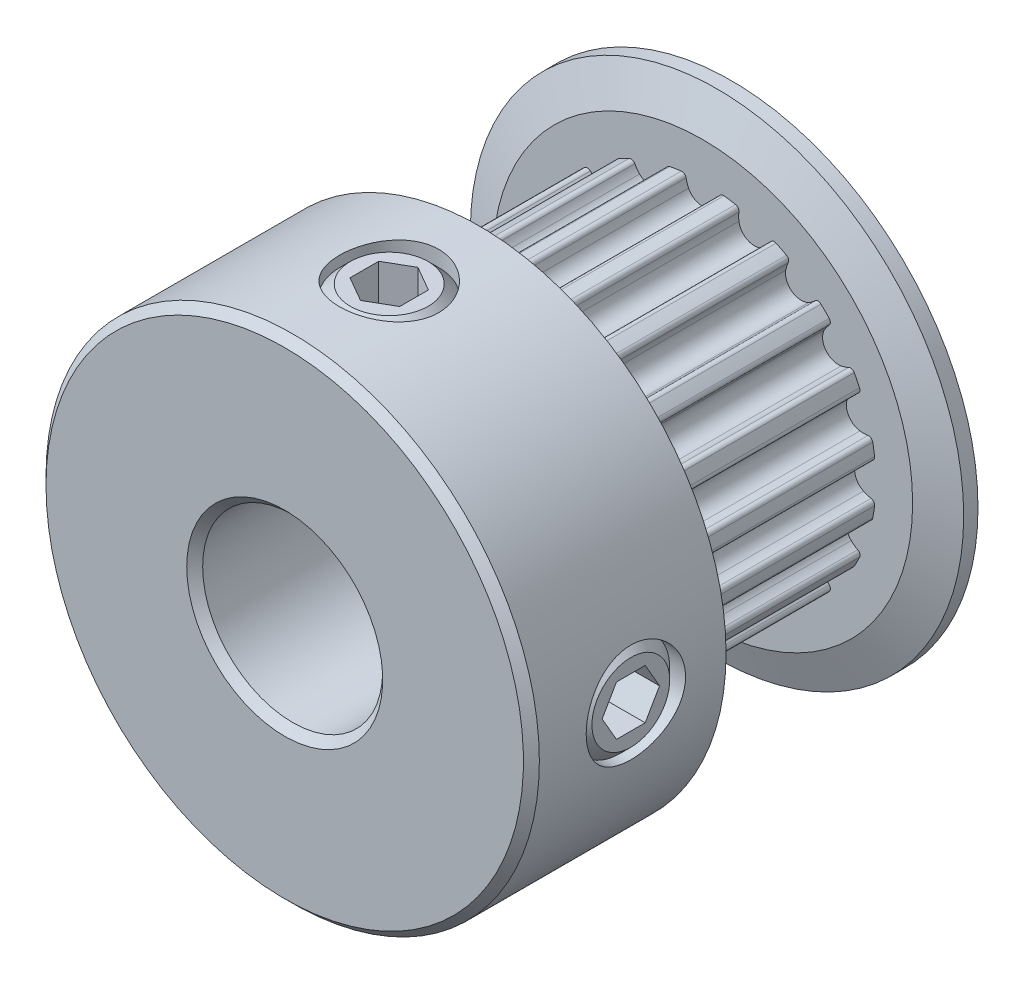
SolidWorks part; units mm, degrees
ref_plane "Front Plane" through (0, 0, 0) normal (0, 0, 1) x (1, 0, 0)
ref_plane "Top Plane" through (0, 0, 0) normal (0, 1, 0) x (1, 0, 0)
ref_plane "Right Plane" through (0, 0, 0) normal (1, 0, 0) x (0, 0, -1)
sketch "Sketch1" plane through (0, 0, 0) normal (0, 0, 1) x (1, 0, 0)
  line L1 (-1.7499, 5.3585) -> (1.7499, 5.3585) construction
  line L4 (0, 0) -> (0, 5.3585) construction
  line L5 (0, 5.3585) -> (0, 11.211) construction
  line L6 (0, 6.3625) -> (1.9751, 6.0482) construction
  line L7 (1.9751, 6.0482) -> (2.6648, 5.8229) construction
  line L8 (1.9751, 6.0482) -> (1.7499, 5.3585) construction
  line L9 (-1.9751, 6.0482) -> (-1.7499, 5.3585) construction
  line L10 (-1.8963, 5.8067) -> (-2.841, 8.6995)
  line L11 (-2.841, 8.6995) -> (2.841, 8.6995)
  line L12 (2.841, 8.6995) -> (1.8963, 5.8067)
  circle A0 centre (0, 0) radius 6.3625 construction
  circle A1 centre (0, 0) radius 8.6995 construction
  circle A2 centre (0, 0) radius 6.1085 construction
  arc A3 (-0.4989, 5.6703) -> (0.4989, 5.6703) centre (0, 5.9135) ccw
  arc A4 (-0.4989, 5.6703) -> (-0.5855, 5.9387) centre (0.4, 6.1085) cw
  arc A5 (-1.8963, 5.8067) -> (-0.7518, 6.0621) centre (0, 0) cw
  arc A6 (-0.5855, 5.9387) -> (-0.7518, 6.0621) centre (-0.7333, 5.9132) ccw
  arc A7 (1.8963, 5.8067) -> (0.7518, 6.0621) centre (0, 0) ccw
  arc A8 (0.5855, 5.9387) -> (0.7518, 6.0621) centre (0.7333, 5.9132) cw
  arc A9 (0.4989, 5.6703) -> (0.5855, 5.9387) centre (-0.4, 6.1085) ccw
  point P6 (0, 20.9083)
  point P11 (0, 6.3625)
  point P13 (0, 8.6995)
  point P14 (0, 6.1085)
  dimension "D1" = 9.6973
  dimension "D2" = 4.8485
sketch "Sketch2" plane through (0, 0, 0) normal (1, 0, 0) x (0, 0, -1)
  line L0 (-7.875, 3.175) -> (7.875, 3.175)
  line L1 (-7.875, 3.175) -> (-7.875, 8.6995)
  line L2 (-1.01, 8.6995) -> (-7.875, 8.6995)
  line L3 (-1.515, 3.175) -> (-1.515, 8.6995) construction
  line L4 (-1.515, 8.6995) -> (-0.505, 8.6995) construction
  line L5 (-0.505, 8.6995) -> (-0.505, 6.1085) construction
  line L6 (-0.505, 6.1085) -> (6.865, 6.1085)
  line L7 (6.865, 6.1085) -> (6.865, 8.6995) construction
  line L8 (6.865, 8.6995) -> (7.875, 8.6995) construction
  line L9 (7.875, 8.6995) -> (7.875, 3.175)
  line L10 (-7.875, 0) -> (7.875, 0) construction
  line L11 (7.37, 8.6995) -> (6.865, 7.404)
  line L12 (-0.505, 7.404) -> (-1.01, 8.6995)
  line L14 (-0.505, 7.404) -> (-0.505, 6.1085)
  line L15 (6.865, 6.1085) -> (6.865, 7.404)
  line L16 (7.37, 8.6995) -> (7.875, 8.6995)
  arc A0 (-0.505, 7.404) -> (-1.01, 8.6995) centre (-2.4192, 7.404) ccw construction
  arc A1 (6.865, 7.404) -> (7.37, 8.6995) centre (8.7792, 7.404) cw construction
  point P12 (-0.505, 7.404)
  point P14 (-1.01, 8.6995)
  point P20 (6.865, 7.404)
  point P21 (7.37, 8.6995)
  point P25 (6.865, 0)
  point P26 (-0.505, 0)
  dimension "OA" = 15.75
  dimension "Bore" = 6.35
  dimension "Outside Width" = 8.38
  dimension "Inside Width" = 7.37
revolve "Revolve1" add sketch "Sketch2" angle 360 mid plane about L10
sketch "Sketch3" plane through (0, 0, 0) normal (0, 0, 1) x (1, 0, 0)
  line L6 (2.841, 8.6995) -> (-2.841, 8.6995)
  line L7 (1.8963, 5.8067) -> (2.841, 8.6995)
  line L8 (-2.841, 8.6995) -> (-1.8963, 5.8067)
  line L9 (2.841, 8.6995) -> (-2.841, 8.6995)
  line L10 (1.8963, 5.8067) -> (2.841, 8.6995)
  line L11 (-2.841, 8.6995) -> (-1.8963, 5.8067)
  arc A8 (1.8963, 5.8067) -> (0.7518, 6.0621) centre (0, 0) ccw
  arc A9 (0.7518, 6.0621) -> (0.5855, 5.9387) centre (0.7333, 5.9132) ccw
  arc A10 (0.4989, 5.6703) -> (0.5855, 5.9387) centre (-0.4, 6.1085) ccw
  arc A11 (-0.4989, 5.6703) -> (0.4989, 5.6703) centre (0, 5.9135) ccw
  arc A12 (-0.5855, 5.9387) -> (-0.4989, 5.6703) centre (0.4, 6.1085) ccw
  arc A13 (-0.5855, 5.9387) -> (-0.7518, 6.0621) centre (-0.7333, 5.9132) ccw
  arc A14 (-0.7518, 6.0621) -> (-1.8963, 5.8067) centre (0, 0) ccw
  arc A15 (1.8963, 5.8067) -> (0.7518, 6.0621) centre (0, 0) ccw
  arc A16 (0.7518, 6.0621) -> (0.5855, 5.9387) centre (0.7333, 5.9132) ccw
  arc A17 (0.4989, 5.6703) -> (0.5855, 5.9387) centre (-0.4, 6.1085) ccw
  arc A18 (-0.4989, 5.6703) -> (0.4989, 5.6703) centre (0, 5.9135) ccw
  arc A19 (-0.5855, 5.9387) -> (-0.4989, 5.6703) centre (0.4, 6.1085) ccw
  arc A20 (-0.5855, 5.9387) -> (-0.7518, 6.0621) centre (-0.7333, 5.9132) ccw
  arc A21 (-0.7518, 6.0621) -> (-1.8963, 5.8067) centre (0, 0) ccw
  dimension "D1" = 0
extrude "Cut-Extrude1" cut sketch "Sketch3" against normal up to vertex (6.865 mm away) from vertex up to point (0, 6.1085, -6.865) starting at point (0, 6.1085, 0.505)
pattern_circular "CirPattern1" count 20 over 360 about axis through (0, 0, 7.875) along (0, 0, 1) of "Cut-Extrude1"
sketch "Sketch4" plane through (0, 0, 0) normal (1, 0, 0) x (0, -1, 0)
  line L0 (0, -0.505) -> (0, -7.875) construction
  line L1 (-3.175, -7.875) -> (3.175, -7.875) construction
  line L2 (7.404, -0.505) -> (-7.404, -0.505) construction
  circle A0 centre (0, -4.19) radius 1.7526
extrude "Cut-Extrude2" cut sketch "Sketch4" along normal through all
ref_plane "Plane1" through (0, 0, 4.19) normal (0, 0, 1) x (1, 0, 0)
sketch "Sketch5" plane through (0, 0, 4.19) normal (0, 0, 1) x (1, 0, 0)
  line L0 (0, 0) -> (0, 8.6995) construction
  line L1 (3.175, -1.3716) -> (3.175, 0)
  line L2 (3.556, -1.7526) -> (8.1401, -1.7526)
  line L3 (3.175, 0) -> (8.6995, 0) construction
  line L4 (3.175, 0) -> (8.5211, 0)
  line L5 (8.5211, 0) -> (8.5211, -1.3716)
  line L6 (3.556, -1.7526) -> (3.175, -1.3716)
  line L7 (8.5211, -1.3716) -> (8.1401, -1.7526)
  circle A0 centre (0, 0) radius 8.6995 construction
  circle A1 centre (0, 0) radius 3.175 construction
  point P2 (3.175, -1.7526)
  point P11 (8.5211, -1.7526)
revolve "Revolve2" add sketch "Sketch5" angle 360 mid plane about L4
sketch "Sketch6" plane through (8.5211, 5.3841, 0) normal (-1, 0, 0) x (0, -1, 0)
  line L1 (5.3841, 5.2019) -> (4.5078, 4.6959)
  line L2 (4.5078, 4.6959) -> (4.5078, 3.6841)
  line L3 (4.5078, 3.6841) -> (5.3841, 3.1781)
  line L4 (5.3841, 3.1781) -> (6.2604, 3.6841)
  line L5 (6.2604, 3.6841) -> (6.2604, 4.6959)
  line L6 (6.2604, 4.6959) -> (5.3841, 5.2019)
  circle A0 centre (5.3841, 4.19) radius 0.8763 construction
  dimension "D1" = 1.7526
extrude "Cut-Extrude3" cut sketch "Sketch6" along normal blind 1.3144
pattern_circular "CirPattern3" count 2 over 90 about axis through (0, 0, 7.875) along (0, 0, 1) of "Cut-Extrude2", "Revolve2", "Cut-Extrude3"
chamfer "Chamfer1" distance 0.2807 angle 45 2 edges at (3.175, 0, 7.875) (8.6995, 0, 7.875)
ref_axis "Center Axis 1" through (0, 0, -7.875) along (0, 0, 1)
ref_plane "Contact Plane 1" through (0, 0, 7.875) normal (0, 0, 1) x (1, 0, 0)
ref_plane "Contact Plane 2" through (0, 0, -7.875) normal (0, 0, -1) x (-1, 0, 0)
equation "\"D2@Sketch1\"= \"D1@Sketch1\" / 2"
equation "\"D1@Sketch6\" = \"Set Screw@Sketch4\" / 2"
equation "\"D1@Cut-Extrude3\" = \"D1@Sketch6\"*.75"
